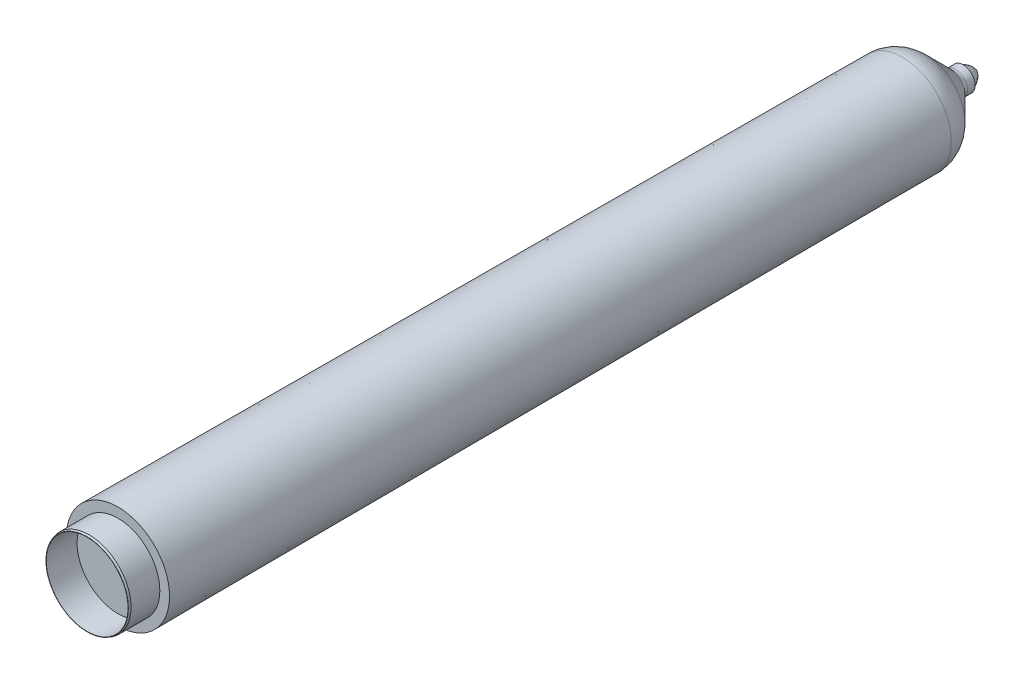
SolidWorks part; units mm, degrees
material "PVC 0.007 Plasticized"
ref_plane "Front Plane" through (0, 0, 0) normal (0, 0, 1) x (1, 0, 0)
ref_plane "Top Plane" through (0, 0, 0) normal (0, 1, 0) x (1, 0, 0)
ref_plane "Right Plane" through (0, 0, 0) normal (1, 0, 0) x (0, 0, -1)
sketch "Sketch1" plane through (0, 0, 0) normal (0, 0, 1) x (1, 0, 0)
  circle A0 centre (0, 0) radius 6.25
  circle A1 centre (0, 0) radius 7.7
  dimension "D1" = 12.5
  dimension "D2" = 15.4
extrude "Boss-Extrude3" add sketch "Sketch1" against normal blind 126.14 draft 0.2 contours A1
sketch "Sketch3" plane through (0, 0, 0) normal (0, 0, 1) x (1, 0, 0)
  circle A0 centre (0, 0) radius 6.1
  circle A1 centre (0, 0) radius 6.25
  dimension "D1" = 12.5
  dimension "D2" = 12.2
extrude "Boss-Extrude4" add sketch "Sketch3" along normal blind 4.6
chamfer "Chamfer2" distance 0.3 distance2 0.1 1 edges at (6.25, 0, 4.6)
sketch "Croquis1" plane through (0, 0, 0) normal (1, 0, 0) x (0, 0, -1)
  line L7 (124.14, 1.5799) -> (124.14, 0)
  line L8 (126.14, 1.7799) -> (124.14, 1.7799)
  line L9 (124.14, 0) -> (126.14, 0)
  line L10 (126.14, -7.2597) -> (126.14, 7.2597) construction
  line L11 (124.14, 1.7799) -> (124.14, 7.2667)
  line L12 (126.14, 7.2597) -> (124.14, 7.2667)
  line L13 (126.14, 1.7799) -> (126.14, 7.2597)
  line L14 (126.14, 1.5799) -> (124.14, 1.5799)
  line L15 (126.14, 0) -> (126.14, 1.5799)
  line L19 (126.14, 7.2597) -> (0, 7.7) construction
  dimension "D1" = 0.2
  dimension "D2" = 2
revolve "Cortar-Revolución1" cut sketch "Croquis1" angle 360 about L9
chamfer "Chaflán1" distance 5 1 edges at (0, -7.2667, -124.14)
fillet "Redondeo2" radius 1 1 edges at (0, -1.7799, -124.14)
fillet "Redondeo4" radius 5 1 edges at (7.2841, 0, -119.14)
sketch "Croquis2" plane through (0, 0, 0) normal (1, 0, 0) x (0, 0, -1)
  line L0 (126.4315, 0) -> (124.14, 0) construction
  line L1 (126.14, 0) -> (126.14, 1.5799)
  line L2 (128.14, 0) -> (126.14, 0)
  arc A0 (126.14, 1.5799) -> (128.14, 0) centre (125.4565, -1.3412) cw
  dimension "D2" = 3
  dimension "D1" = 2
revolve "Revolución1" add sketch "Croquis2" angle 360 about L0
